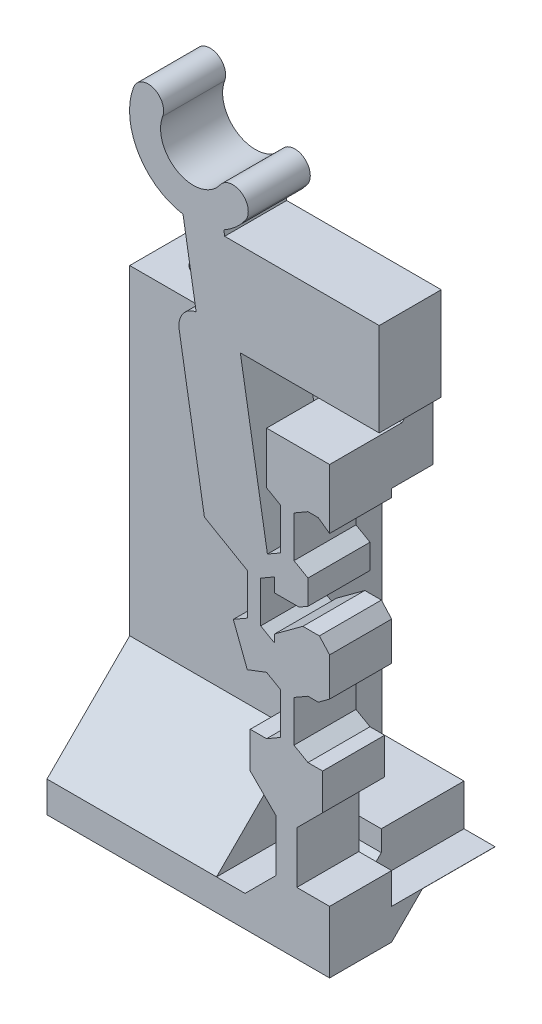
SolidWorks part; units mm, degrees
material "Nylon 6/12"
ref_plane "Front Plane" through (0, 0, 0) normal (0, 0, 1) x (1, 0, 0)
ref_plane "Top Plane" through (0, 0, 0) normal (0, 1, 0) x (1, 0, 0)
ref_plane "Right Plane" through (0, 0, 0) normal (1, 0, 0) x (0, 0, -1)
sketch "Sketch-SkeletonConfigUp" plane through (0, 0, 0) normal (0, 0, 1) x (1, 0, 0)
  line L0 (0, 0) -> (0, -50000) construction
  line L1 (0, 0) -> (4.5811, 6.2164) construction
  line L2 (9.8143, 13.3177) -> (4.5811, 13.945) construction
  line L3 (4.5811, 13.945) -> (2.9713, 10.4094) construction
  line L4 (2.9713, 10.4094) -> (4.5811, 6.2164) construction
  line L5 (4.5811, 13.945) -> (6.2429, 19.1409) construction
  line L6 (2.9713, 10.4094) -> (0.0405, 27.8193) construction
  line L7 (4.5811, 6.2164) -> (9.8143, 13.3177) construction
  line L8 (-587.3593, -797.0242) -> (9.8143, 13.3177) construction
  dimension "D2" = 7.7221
  dimension "D3" = 8.8212
  dimension "D4" = 5.2707
  dimension "D5" = 119.553
  dimension "D6" = 3.8848
  dimension "D7" = 5.4552
  dimension "D8" = 17.6549
  dimension "D9" = 4.4914
  dimension "D10" = 6.745
  dimension "D11" = 145.964
  dimension "D12" = 143.612
sketch "Sketch-SkeletonConfigDown" plane through (0, 0, 0) normal (0, 0, 1) x (1, 0, 0)
  line L0 (0, 0) -> (0, -50000) construction
  line L1 (0, 0) -> (4.5811, 6.2164) construction
  line L2 (9.8143, 13.3177) -> (4.5811, 13.945) construction
  line L3 (4.5811, 13.945) -> (6.1909, 10.4094) construction
  line L4 (6.1909, 10.4094) -> (4.5811, 6.2164) construction
  line L5 (4.5811, 13.945) -> (1.753, 18.6098) construction
  line L6 (6.1909, 10.4094) -> (-8.8652, 19.6294) construction
  line L7 (4.5811, 6.2164) -> (9.8143, 13.3177) construction
  line L8 (-589.9357, -800.5203) -> (9.8143, 13.3177) construction
  dimension "D2" = 7.7221
  dimension "D3" = 8.8212
  dimension "D4" = 5.2707
  dimension "D5" = 119.553
  dimension "D6" = 3.8848
  dimension "D7" = 5.4552
  dimension "D8" = 17.6549
  dimension "D9" = 4.4914
  dimension "D10" = 6.745
  dimension "D11" = 145.964
  dimension "D1" = 143.612
ref_plane "Plane-Cam Base" through (9.128, 0, 0) normal (1, 0, 0) x (0, 0, -1)
ref_plane "Plane-Down-to-Up Derailleur Clearance" through (6.628, 0, 0) normal (1, 0, 0) x (0, 0, -1)
ref_plane "Plane-Cam Cavity Roof" through (5.128, 0, 0) normal (1, 0, 0) x (0, 0, -1)
sketch "Sketch-SwitchBossUp" plane through (0, 0, 0) normal (0, 0, 1) x (1, 0, 0)
  line L0 (3.5811, 11.4759) -> (3.5811, 12.945) construction
  line L5 (5.5811, 12.5549) -> (5.5811, 11.3705)
  line L7 (1.5115, 25.1048) -> (1.5536, 24.8548)
  line L8 (-0.4607, 24.7728) -> (1.6966, 11.9577) construction
  line L9 (2.9713, 10.4094) -> (0.0405, 27.8193) construction
  line L11 (0.1364, 21.2256) -> (2.1086, 21.5576) construction
  line L15 (6.628, -23.7286) -> (6.628, 23.7286) construction
  line L16 (2.9713, 10.4094) -> (4.5811, 6.2164) construction
  line L17 (3.5811, 12.945) -> (3.5811, 14.945) construction
  line L18 (5.5811, 12.945) -> (5.5811, 14.945) construction
  line L19 (4.2561, 13.945) -> (4.9061, 13.945) construction
  line L20 (3.5811, 14.945) -> (5.5811, 14.945) construction
  line L21 (3.5811, 12.945) -> (5.5811, 12.945) construction
  line L22 (4.5811, 12.945) -> (4.5811, 14.945) construction
  line L23 (4.5811, 6.2164) -> (8.5404, 7.1023) construction
  line L24 (1.9713, 9.4094) -> (1.9713, 11.4094) construction
  line L25 (3.9713, 9.4094) -> (3.9713, 11.4094) construction
  line L26 (3.9713, 9.4094) -> (1.9713, 9.4094) construction
  line L27 (1.9713, 11.4094) -> (3.9713, 11.4094) construction
  line L28 (3.5811, 7.2164) -> (5.5811, 7.2164) construction
  line L29 (3.5811, 7.2164) -> (3.5811, 5.2164) construction
  line L30 (5.5811, 7.2164) -> (5.5811, 5.2164) construction
  line L31 (3.5811, 5.2164) -> (5.5811, 5.2164) construction
  line L32 (4.9061, 6.2164) -> (4.2561, 6.2164) construction
  line L40 (3.2963, 10.4094) -> (2.6463, 10.4094) construction
  line L66 (0.0405, 27.8193) -> (0.0405, 50027.8193) construction
  line L75 (4.5811, 3.3049) -> (4.5405, -0.6733) construction
  line L76 (5.5811, 11.3705) -> (5.5811, 12.5549) construction
  line L81 (9.1185, 1033.2334) -> (9.1185, 20.05) construction
  line L85 (6.9307, 9.5241) -> (9.1185, 7.0942) construction
  line L88 (5.7256, 17.835) -> (6.628, 17.835)
  line L92 (3.7762, 8.3129) -> (6.9307, 9.5241) construction
  line L101 (4.5811, 6.2164) -> (6.9307, 9.5241) construction
  line L103 (0.0405, 27.8193) -> (1.9448, 26.4638) construction
  line L104 (6.9307, 9.5241) -> (9.1185, 7.0942) construction
  line L107 (1.9713, 9.4094) -> (1.9713, 9.0197) construction
  line L109 (0.0405, 27.8193) -> (-2.1498, 28.6358) construction
  line L111 (6.628, 9.8603) -> (6.628, 8.0076)
  line L112 (6.628, 9.8603) -> (6.9307, 9.5241) construction
  line L114 (7.3693, 7.7363) -> (7.3563, 7.7363) construction
  line L121 (5.0405, -1.6882) -> (5.0405, -0.6733) construction
  line L122 (9.028, 22.3548) -> (9.028, 20.3548)
  line L127 (5.5811, 15.3347) -> (5.5811, 14.945) construction
  line L133 (2.9713, 10.4094) -> (6.1909, 10.4094) construction
  line L134 (4.5811, 10.4094) -> (4.5811, 13.945) construction
  line L135 (4.5811, 10.4094) -> (4.5811, 6.2164) construction
  line L137 (3.9713, 9.4094) -> (5.5811, 7.2164) construction
  line L139 (5.3335, 10.4094) -> (3.9713, 9.4094)
  line L142 (2.5405, -2.1733) -> (2.5405, -3.6733)
  line L143 (9.1185, 20.05) -> (9.1185, 18.3248) construction
  line L145 (9.1185, 16.5986) -> (9.1185, -49992.4252) construction
  line L147 (5.5811, 11.3705) -> (5.5811, 12.5549) construction
  line L150 (2.5405, -3.6733) -> (6.628, -3.6733)
  line L151 (4.0405, 1.8267) -> (5.0405, 1.8267) construction
  line L152 (4.2555, 14.945) -> (4.2555, 12.945)
  line L153 (4.9055, 14.945) -> (4.9055, 12.945)
  line L157 (3.5811, 17.835) -> (3.5811, 15.335)
  line L162 (3.2963, 11.4094) -> (3.2963, 9.4094)
  line L164 (2.6463, 11.4094) -> (2.6463, 9.4094)
  line L169 (4.2561, 7.2164) -> (4.2561, 5.2164)
  line L170 (4.9061, 5.2164) -> (4.9061, 7.2164)
  line L175 (4.2561, 7.2164) -> (3.5811, 7.6061)
  line L176 (4.9061, 7.2164) -> (5.5811, 7.6061)
  line L177 (5.5811, 7.2164) -> (5.5811, 7.6061) construction
  line L179 (4.2561, 5.2164) -> (3.5811, 4.8267)
  line L180 (3.5811, 5.2164) -> (3.5811, 4.8267) construction
  line L181 (3.5811, 4.8267) -> (2.7905, 4.8267)
  line L183 (4.9061, 5.2164) -> (5.5811, 4.8267)
  line L184 (5.5811, 5.2164) -> (5.5811, 4.8267) construction
  line L186 (9.128, -23.7286) -> (9.128, 23.7286) construction
  line L187 (2.6463, 9.4094) -> (1.9713, 9.0197)
  line L188 (3.2963, 9.4094) -> (3.9713, 9.0197)
  line L189 (3.2963, 11.4094) -> (3.9713, 11.7991)
  line L190 (2.6463, 11.4094) -> (1.6966, 11.9577)
  line L191 (3.9713, 11.4094) -> (3.9713, 11.7991) construction
  line L192 (3.9713, 11.7991) -> (3.9713, 11.1241)
  line L193 (4.9055, 12.945) -> (5.5811, 12.5549)
  line L194 (4.2555, 12.945) -> (3.6202, 12.5782)
  line L195 (3.9713, 11.1241) -> (5.1543, 11.1241)
  line L196 (3.9713, 9.4094) -> (3.9713, 9.0197)
  line L197 (3.5811, 7.2164) -> (3.5811, 7.6061) construction
  line L199 (3.5811, 7.6061) -> (2.6469, 7.2496)
  line L201 (2.7905, 3.0767) -> (2.7905, 4.8267)
  line L202 (2.7905, 3.0767) -> (6.2905, 3.0767) construction
  line L207 (9.1185, 18.3248) -> (9.1185, 16.5986) construction
  line L208 (6.628, -3.6733) -> (6.628, -0.6733)
  line L209 (9.1185, 20.05) -> (9.1185, 16.5986) construction
  line L211 (5.0405, -0.6733) -> (5.0405, 1.8267)
  line L212 (4.0405, -0.6733) -> (4.0405, 1.8267)
  line L214 (4.2555, 14.945) -> (3.5798, 15.335)
  line L215 (3.5798, 15.335) -> (3.5811, 15.335)
  line L216 (4.9055, 14.945) -> (5.5811, 15.335)
  line L217 (5.5811, 12.945) -> (5.5811, 12.5549) construction
  line L218 (4.9055, 14.945) -> (4.9055, 15.335) construction
  line L219 (5.5811, 15.335) -> (3.5798, 15.335) construction
  line L221 (9.028, 22.3548) -> (9.028, 24.8548)
  line L224 (3.5811, 17.835) -> (5.7256, 17.835)
  line L232 (6.628, 14.945) -> (6.628, 17.835)
  line L236 (1.5536, 24.8548) -> (9.028, 24.8548)
  line L250 (9.028, 20.3548) -> (2.3111, 20.3548)
  line L254 (5.0405, -0.6733) -> (4.0405, -0.6733) construction
  line L255 (4.0405, -0.6733) -> (3.0345, -0.6733) construction
  line L256 (4.5811, 6.2164) -> (4.5811, 3.3049) construction
  line L259 (5.0405, -0.6733) -> (6.628, -0.6733)
  line L261 (1.6966, 11.9577) -> (0.5733, 12.6062)
  line L262 (0.5733, 12.6062) -> (-0.6452, 19.8444)
  line L263 (4.0405, 1.8267) -> (2.7905, 3.0767)
  line L266 (5.0405, 1.8267) -> (6.2905, 3.0767)
  line L270 (2.5405, -2.1733) -> (4.0405, -0.6733)
  line L279 (0.175, 20.9965) -> (-0.4607, 24.7728)
  line L283 (2.3111, 20.3548) -> (3.6202, 12.5782)
  line L367 (5.5811, 4.8267) -> (6.2905, 4.8267)
  line L368 (6.2905, 4.8267) -> (6.2905, 3.0767)
  line L471 (2.6469, 7.2496) -> (1.9713, 9.0197)
  line L472 (6.1335, 10.4094) -> (6.628, 9.8603)
  line L473 (5.3335, 10.4094) -> (6.1335, 10.4094)
  line L474 (5.5811, 7.6061) -> (6.0811, 7.6061)
  line L475 (6.0811, 7.6061) -> (6.628, 8.0076)
  line L477 (5.1543, 11.1241) -> (5.5811, 11.3705)
  line L478 (5.5811, 15.335) -> (6.0811, 15.335)
  line L479 (5.5811, 14.945) -> (6.9307, 14.945) construction
  line L480 (6.628, 14.945) -> (6.0811, 15.335)
  arc A0 (1.5115, 25.1048) -> (2.5558, 26.0289) centre (0.0405, 27.8193) ccw
  arc A1 (-1.5413, 25.1678) -> (-2.8525, 28.8978) centre (0.0405, 27.8193) cw
  arc A2 (-2.8525, 28.8978) -> (-1.447, 28.3738) centre (-2.1498, 28.6358) cw
  arc A3 (2.5558, 26.0289) -> (1.3338, 26.8987) centre (1.9448, 26.4638) ccw
  arc A4 (-1.447, 28.3738) -> (1.3338, 26.8987) centre (0.0405, 27.8193) ccw
  arc A5 (3.5811, 12.945) -> (3.5811, 14.945) centre (3.1778, 13.945) ccw construction
  arc A6 (5.5811, 12.945) -> (5.5811, 14.945) centre (5.9843, 13.945) cw construction
  arc A7 (2.528, 9.9183) -> (1.9713, 11.4094) centre (1.568, 10.4094) ccw construction
  arc A8 (3.9713, 11.4094) -> (3.9713, 9.4094) centre (4.3745, 10.4094) ccw construction
  arc A9 (3.5811, 7.2164) -> (3.5811, 5.2164) centre (3.1779, 6.2164) cw construction
  arc A10 (5.5811, 7.2164) -> (5.5811, 5.2164) centre (5.9844, 6.2164) ccw construction
  circle A28 centre (0.0405, 27.8193) radius 2.3375 construction
  arc A29 (1.9713, 9.4094) -> (2.528, 9.9183) centre (1.568, 10.4094) ccw construction
  arc A38 (-0.6452, 19.8444) -> (0.175, 20.9965) centre (0.341, 20.0104) cw
  arc A39 (-1.5413, 25.1678) -> (-0.4607, 24.7728) centre (0.0405, 27.8193) ccw
  point P53 (4.5811, 13.945)
  point P63 (2.9713, 10.4094)
  point P93 (1.1225, 21.3916)
  dimension "D23" = 1.5875
  dimension "D24" = 0.75
  dimension "D2" = 2
  dimension "D5" = 2
  dimension "D16" = 42
  dimension "D27" = 120
  dimension "D28" = 120
  dimension "D29" = 120
  dimension "D30" = 120
  dimension "D31" = 120
  dimension "D32" = 120
  dimension "D33" = 120
  dimension "D34" = 120
  dimension "D21" = 2.5
  dimension "D38" = 2
  dimension "D42" = 45
  dimension "D43" = 120
  dimension "D15" = 0.25
  dimension "D6" = 0.65
  dimension "D12" = 1
  dimension "D19" = 0.65
  dimension "D20" = 1
  dimension "D18" = 1.5
  dimension "D36" = 3
  dimension "D37" = 2.5
  dimension "D44" = 5
  dimension "D73" = 2.5
  dimension "D10" = 45
  dimension "D74" = 3.5
  dimension "D75" = 3
  dimension "D76" = 1
  dimension "D8" = 42
  dimension "D39" = 0.8
  dimension "D40" = 0.5
  dimension "D41" = 0.675
  dimension "D77" = 1.183
  dimension "D25" = 120
  dimension "D26" = 120
  dimension "D78" = 120
  dimension "D35" = 120
  dimension "D79" = 0.5
extrude "Boss-Switch Body" add sketch "Sketch-SwitchBossUp" along normal blind 3
sketch "Sketch1" plane through (0, 0, 0) normal (0, 0, -1) x (-1, 0, 0)
  line L1 (-6.628, -3.6733) -> (-2.5405, -3.6733)
  line L2 (-6.628, -3.6733) -> (-6.628, -2.1733)
  line L4 (-2.5405, -3.6733) -> (-2.5405, -2.1733)
  line L5 (-3.5811, 18.835) -> (-6.628, 18.835)
  line L10 (-6.628, 18.835) -> (-6.628, 15.335)
  line L12 (-6.628, 15.335) -> (-3.5811, 15.335)
  line L13 (-6.628, -2.1733) -> (-2.5405, -2.1733)
  line L14 (-3.5811, 15.335) -> (-3.5811, 18.835)
  line L22 (-2.5405, -3.6733) -> (-6.628, -3.6733) construction
  line L25 (-6.628, -3.6733) -> (-6.628, -0.6733) construction
  dimension "D1" = 3.5
extrude "Boss-Flange Width" add sketch "Sketch1" along normal blind 5
ref_plane "Plane-Sta2Sit Groove" through (0.0405, 0, 0) normal (1, 0, 0) x (0, 0, -1)
ref_plane "Plane-Cam Outer Surface" through (-12.0395, 0, 0) normal (1, 0, 0) x (0, 0, -1)
ref_plane "Plane-FlangeTop" through (-7.0395, 0, 0) normal (1, 0, 0) x (0, 0, -1)
sketch "Sketch2" plane through (-7.0395, 0, 0) normal (1, 0, 0) x (0, 0, -1)
  line L0 (5, 15.335) -> (0, 15.335) construction
  line L1 (5, 17.335) -> (1, 17.335)
  line L2 (5, 17.335) -> (5, 15.335)
  line L3 (5, 15.335) -> (1, 15.335)
  line L4 (1, 17.335) -> (1, 15.335)
  line L5 (-3, -3.6733) -> (-3, -0.6733) construction
  line L12 (5, -2.1733) -> (5, -3.6733)
  line L13 (5, -3.6733) -> (-3, -3.6733)
  line L14 (-3, -2.1733) -> (-3, -3.6733)
  line L15 (0, 10.4094) -> (0, 27.8193) construction
  line L16 (1, 15.335) -> (1, -0.6733) construction
  line L22 (5, -2.1733) -> (0, -2.1733) construction
  line L23 (5, -2.1733) -> (-3, -2.1733)
  dimension "D1" = 1
  dimension "D2" = 2
  dimension "D3" = 16.0083
extrude "Boss-Flange Height" add sketch "Sketch2" along normal up to surface (10.6206 mm away) up to face at (3.5811, 17.0493, -0.5714)
sketch "Sketch10" plane through (0, 15.335, 0) normal (0, 1, 0) x (1, 0, 0)
  line L0 (9.128, -23.7286) -> (9.128, 23.7286) construction
  line L1 (6.628, 5) -> (5.128, 5)
  line L2 (6.628, 5) -> (6.628, 2)
  line L3 (6.628, 2) -> (5.128, 2)
  line L5 (4.628, 7) -> (4.628, 0.64) construction
  line L6 (3.5811, 1) -> (-7.0395, 1) construction
  line L8 (5.128, 5) -> (5.128, 2)
  dimension "D1" = 1
  dimension "D2" = 0.5
  dimension "D3" = 4.5
extrude "Cut-Up-To-Down Derailleur Clearance" cut sketch "Sketch10" along normal up to next
sketch "Sketch17" plane through (0, 15.335, 0) normal (0, -1, 0) x (1, 0, 0)
  line L0 (5.128, -5) -> (-7.0395, -5)
  line L1 (5.128, -5) -> (-7.0395, -5) construction
  line L2 (-7.0395, -5) -> (-7.0395, -1)
  line L3 (-7.0395, -1) -> (5.128, -1)
  line L4 (5.128, -1) -> (5.128, -5)
  line L5 (-7.0395, -1) -> (-7.0395, -5) construction
  line L6 (5.128, -5) -> (5.128, -2) construction
extrude "Boss-Flange Support" add sketch "Sketch17" along normal up to surface (17.5083 mm away) up to face at (0.7096, -2.1733, -0.6667)
sketch "Sketch-HolePositions" plane through (0, -3.6733, 0) normal (0, -1, 0) x (1, 0, 0)
  line L0 (-7.0395, -3) -> (6.628, -3) construction
  line L1 (6.628, -5) -> (-7.0395, -5) construction
  line L2 (6.628, -5) -> (6.628, 3) construction
  line L4 (-7.0395, -22.2167) -> (-7.0395, 22.2167) construction
  point P6 (-5.0395, -3)
  point P7 (-0.5395, -3)
  dimension "D1" = 2
  dimension "D2" = 4.5
  dimension "D3" = 2
sketch "Sketch6" plane through (0, -3.6733, 0) normal (0, -1, 0) x (-1, 0, 0)
  point P0 (5.0395, 3)
  point P3 (0.5395, 3)
hole_wizard "Tap Drill for M2x0.4 Tap1" positions "Sketch6" profile "Sketch5" hole size "M2x0.4" standard "ANSI Metric" end condition through all
sketch "Sketch5" plane through (-5.0395, -3.6733, -3) normal (1, 0, 0) x (0, 0, -1)
  line L0 (0, 0) -> (0, 33.0591)
  line L1 (0, 33.0591) -> (0.8, 33.0591)
  line L2 (0.8, 33.0591) -> (0.8, 0)
  line L5 (0.8, 0) -> (0, 0)
  line L11 (0, -6.35) -> (0, 107.95) construction
  dimension "Thru Hole Dia." = 1.6
  dimension "Thru Hole Depth" = 33.0591
sketch "Sketch9" plane through (0, -3.6733, 0) normal (0, -1, 0) x (1, 0, 0)
  point P0 (-5.0395, -3)
  point P3 (-0.5395, -3)
hole_wizard "M2 Clearance Hole2" positions "Sketch9" profile "Sketch8" hole size "M2" standard "ANSI Metric"
sketch "Sketch8" plane through (-5.0395, -3.6733, -3) normal (1, 0, 0) x (0, 0, -1)
  line L0 (0, 0) -> (0, 15.721)
  line L1 (0, 15.721) -> (1.2, 15)
  line L2 (1.2, 15) -> (1.2, 0)
  line L5 (1.2, 0) -> (0, 0)
  line L10 (0, 15.721) -> (-1.2, 15) construction
  line L11 (0, -6.35) -> (0, 107.95) construction
  dimension "Hole Dia." = 2.4
  dimension "Hole Depth" = 15
  dimension "Drill Angle" = 118
sketch "Sketch-Measurements for Derailleur Ramps" [suppressed] plane through (0, 0, 0) normal (0, 0, 1) x (1, 0, 0)
  line L0 (3.184, 15.1695) -> (2.4687, 19.4188)
  line L1 (2.8264, 17.2941) -> (1.8402, 17.1281)
  line L2 (2.9713, 10.4094) -> (0.0405, 27.8193) construction
  line L3 (1.8402, 17.1281) -> (-1.3081, 15.0016)
  line L4 (6.1909, 10.4094) -> (-8.8652, 19.6294) construction
  line L5 (1.8402, 17.1281) -> (2.6012, 12.6077)
  line L6 (2.6012, 12.6077) -> (-1.3081, 15.0016)
  line L7 (0.2661, 16.0649) -> (0.2661, 17.1281)
  line L8 (0.2661, 17.1281) -> (1.8402, 17.1281)
  line L9 (6.1909, 10.4094) -> (2.9713, 10.4094)
  line L10 (5.386, 8.3129) -> (3.7762, 8.3129)
  line L11 (2.6116, 18.5698) -> (1.5115, 25.1048) construction
  line L12 (6.1909, 10.4094) -> (4.5811, 6.2164) construction
  line L13 (4.5811, 8.3129) -> (4.5811, 8.7912)
  line L14 (4.5811, 6.2164) -> (5.386, 8.3129)
  line L15 (2.9713, 10.4094) -> (4.5811, 6.2164) construction
  line L16 (3.7762, 8.3129) -> (4.5811, 6.2164)
  line L17 (5.386, 8.3129) -> (5.386, 8.7912)
  dimension "D1" = 1.5742
  dimension "D2" = 0.8049
ref_plane "Plane1" through (0, 7.1023, 0) normal (0, 1, 0) x (1, 0, 0)
ref_plane "Plane-Cantilever Cut" [suppressed] through (7.0848, 8.5204, -1.9058) normal (-0.6301, -0.7578, 0.1695) x (-0.7765, 0.6151, -0.1368)
sketch "Sketch14" [suppressed] plane through (7.0848, 8.5204, -1.9058) normal (-0.6301, -0.7578, 0.1695) x (-0.7765, 0.6151, -0.1368)
  line L0 (2.3023, -1.6911) -> (-0.3551, -1.6911)
  line L2 (2.3023, -4.3362) -> (2.3023, -1.6911)
  line L3 (-0.3551, -1.6911) -> (-0.3551, -4.4608)
  line L5 (-0.3551, -4.4608) -> (1.0087, -5.0843)
  line L6 (1.0087, -5.0843) -> (2.3023, -4.3362)
extrude "Cut-Down-to-Up Cantilever Slope" [suppressed] cut sketch "Sketch14" against normal up to next
ref_plane "Plane-Symmetry Plane" through (0, 0, 1.5) normal (0, 0, 1) x (1, 0, 0)
sketch "Sketch-Cable Center Point" plane through (0, 0, 1.5) normal (0, 0, 1) x (1, 0, 0)
  line L0 (0.0405, 27.8193) -> (0.1722, 27.0366)
  line L1 (2.9713, 10.4094) -> (0.0405, 27.8193) construction
  point P0 (0.0405, 27.8193)
  dimension "D1" = 0.7937
chamfer "Chamfer-Flange Support" distance 1.5 angle 45 1 edges at (3.5811, 17.335, -3)
chamfer "Chamfer-Flange Support 2" distance 1.5 angle 45 2 edges at (5.128, 17.085, -2) (5.128, 15.335, -1.5)
chamfer "Chamfer7" [suppressed] distance 1 angle 45
sketch "Sketch23" plane through (0, 0, -1) normal (0, 0, 1) x (1, 0, 0)
  line L0 (8.5102, -0.1733) -> (1.1605, -0.1733)
  line L2 (1.1605, -0.1733) -> (1.1605, 15.335)
  line L3 (1.1605, 15.335) -> (8.5102, 15.335)
  line L4 (8.5102, 15.335) -> (8.5102, -0.1733)
  line L5 (0.6605, -3.6733) -> (0.6605, 11.3267) construction
  line L8 (5.5811, 15.335) -> (3.5811, 15.335) construction
  line L11 (2.5405, -2.1733) -> (-7.0395, -2.1733) construction
  dimension "D1" = 0.5
  dimension "D2" = 2
extrude "Cut-Gap for Printing" cut sketch "Sketch23" against normal through all
sketch "Sketch27" plane through (5.128, 0, 0) normal (1, 0, 0) x (0, 0, -1)
  line L0 (3.5, 18.835) -> (3.5, 15.335) construction
  line L1 (2.5, 18.835) -> (5, 18.835)
  line L2 (2.5, 18.835) -> (2.5, 15.335)
  line L3 (2.5, 15.335) -> (5, 15.335)
  line L4 (5, 18.835) -> (5, 15.335)
  line L5 (5, 18.835) -> (5, 15.335) construction
  line L6 (2, 18.835) -> (3.5, 18.835) construction
  line L8 (5, 15.335) -> (3.5, 15.335) construction
  dimension "D1" = 1
extrude "Cut-Wide Derailleur Clearance" cut sketch "Sketch27" against normal blind 4 and the other way through all
chamfer "Chamfer9" distance 1.25 angle 45 1 edges at (4.8545, 18.835, -2.5)
sketch "Sketch28" plane through (0, 0, -1) normal (0, 0, 1) x (1, 0, 0)
  line L0 (3.5811, 18.835) -> (6.628, 18.835)
  line L1 (6.628, 18.835) -> (6.628, 17.835)
  line L2 (6.628, 17.835) -> (3.5811, 17.835)
  line L3 (3.5811, 17.835) -> (3.5811, 18.835)
extrude "Cut-Extrude1" cut sketch "Sketch28" along normal up to surface (1 mm away) up to face at (5.1045, 18.335, 0)
chamfer "Chamfer10" distance 0.5 angle 45 2 edges at (5.1045, 17.835, -1) (3.5811, 16.585, -1)
chamfer "Chamfer-Flange Support 3" distance 1 angle 45 1 edges at (-0.9558, -2.1733, -1)
sketch "Sketch31" plane through (-7.0395, 0, 0) normal (-1, 0, 0) x (0, 0, 1)
  line L0 (-5, -2.1807) -> (-5, -3.6733)
  line L1 (-5, -3.6733) -> (-5, 17.335) construction
  line L2 (-5, -3.6733) -> (0, -3.6733)
  line L3 (0, 200000) -> (0, -250000) construction
  line L4 (3, -3.6733) -> (-5, -3.6733) construction
  line L5 (0, -3.6733) -> (-1.4926, -2.1807)
  line L7 (-1.4926, -2.1807) -> (-5, -2.1807)
  line L8 (0, -2.1733) -> (-1, -1.1733) construction
  dimension "D1" = 30
extrude "Cut-Extrude2" cut sketch "Sketch31" against normal through all
sketch "Sketch32" plane through (-7.0395, 0, 0) normal (-1, 0, 0) x (0, 0, 1)
  line L0 (3, -2.1733) -> (-1, 1.8267)
  line L1 (-1, 17.335) -> (-1, -1.1733) construction
  line L2 (-1, 1.8267) -> (-1, -2.0828)
  line L3 (-1, -2.0828) -> (0.4063, -3.3555)
  line L4 (0.4063, -3.3555) -> (3, -3.3555)
  line L5 (3, -2.1733) -> (3, -3.6733) construction
  line L6 (3, -3.3555) -> (3, -2.1733)
  line L7 (3, -2.1733) -> (0, -2.1733) construction
  dimension "D1" = 45
extrude "Boss-Extrude2" add sketch "Sketch32" against normal up to surface (8.2 mm away) up to face at (1.1605, 9.1317, -2.9)
equation "\"axle-diameter\"=2"
equation "\"switch-thickness\"=12"
equation "\"base-width\"=4.0"
equation "\"axle-bushing-radius\"=3"
equation "\"clearance\"= 0.25"
equation "\"arm-width\"=1.5"
equation "\"min-diameter\"=70"
equation "\"alpha\"=143.6120"
equation "\"gamma\"=119.5526"
equation "\"delta\"=145.9637"
equation "\"epsilon\"=6.7452"
equation "\"l_AB\"=8.8212"
equation "\"l_AC\"=4.4914"
equation "\"l_BD\"=5.2707"
equation "\"l_CD\"=3.8848"
equation "\"l_CE\"=17.6549"
equation "\"l_DF\"=5.4552"
equation "\"l_OA\"=7.7221"
equation "\"D2@Sketch-SkeletonConfigUp\" = \"l_OA\""
equation "\"D3@Sketch-SkeletonConfigUp\" = \"l_AB\""
equation "\"D4@Sketch-SkeletonConfigUp\" = \"l_BD\""
equation "\"D5@Sketch-SkeletonConfigUp\" = \"gamma\""
equation "\"D6@Sketch-SkeletonConfigUp\" = \"l_CD\""
equation "\"D7@Sketch-SkeletonConfigUp\" = \"l_DF\""
equation "\"D8@Sketch-SkeletonConfigUp\" = \"l_CE\""
equation "\"D9@Sketch-SkeletonConfigUp\" = \"l_AC\""
equation "\"D_groove\"=3.175"
equation "\"D7@Sketch-SkeletonConfigDown\" = \"l_DF\""
equation "\"D6@Sketch-SkeletonConfigDown\" = \"l_CD\""
equation "\"D2@Sketch-SkeletonConfigDown\" = \"l_OA\""
equation "\"D3@Sketch-SkeletonConfigDown\" = \"l_AB\""
equation "\"D9@Sketch-SkeletonConfigDown\" = \"l_AC\""
equation "\"D8@Sketch-SkeletonConfigDown\" = \"l_CE\""
equation "\"D5@Sketch-SkeletonConfigDown\" = \"gamma\""
equation "\"D4@Sketch-SkeletonConfigDown\" = \"l_BD\""
equation "\"D1@Sketch-SkeletonConfigDown\" = \"alpha\""
equation "\"hinge_length\"=1.5"
equation "\"hinge_depth\"=0.25"
equation "\"D10@Sketch-SkeletonConfigUp\"=\"epsilon\""
equation "\"D11@Sketch-SkeletonConfigUp\"=\"delta\""
equation "\"D12@Sketch-SkeletonConfigUp\"=\"alpha\""
equation "\"D11@Sketch-SkeletonConfigDown\"=\"delta\""
equation "\"D10@Sketch-SkeletonConfigDown\"=\"epsilon\""
equation "\"EE_dx\"=8.9056"
equation "\"EE_dy\"=8.1898"
equation "\"r_groove\"=\"D_groove\"/2"
equation "\"t_wall\"=25.4/16"
equation "\"width_lower\"=\"D_groove\"+\"t_wall\""
equation "\"cable_to_bottom\"=30.6257"
equation "\"switch_EE-up_base_dy\"=24"
equation "\"switch_EE-down_base_dy\"=16"
equation "\"D_axle\"=25.4/8"
equation "\"D_up_to_down\"=16"
equation "\"D_down_to_up\"=25"
equation "\"t_cam_base\"=7.5"
equation "\"D23@Sketch-SwitchBossUp\"=\"D_groove\"/2"
equation "\"D1@Sketch-Cable Center Point\"=\"D_groove\"/4"
